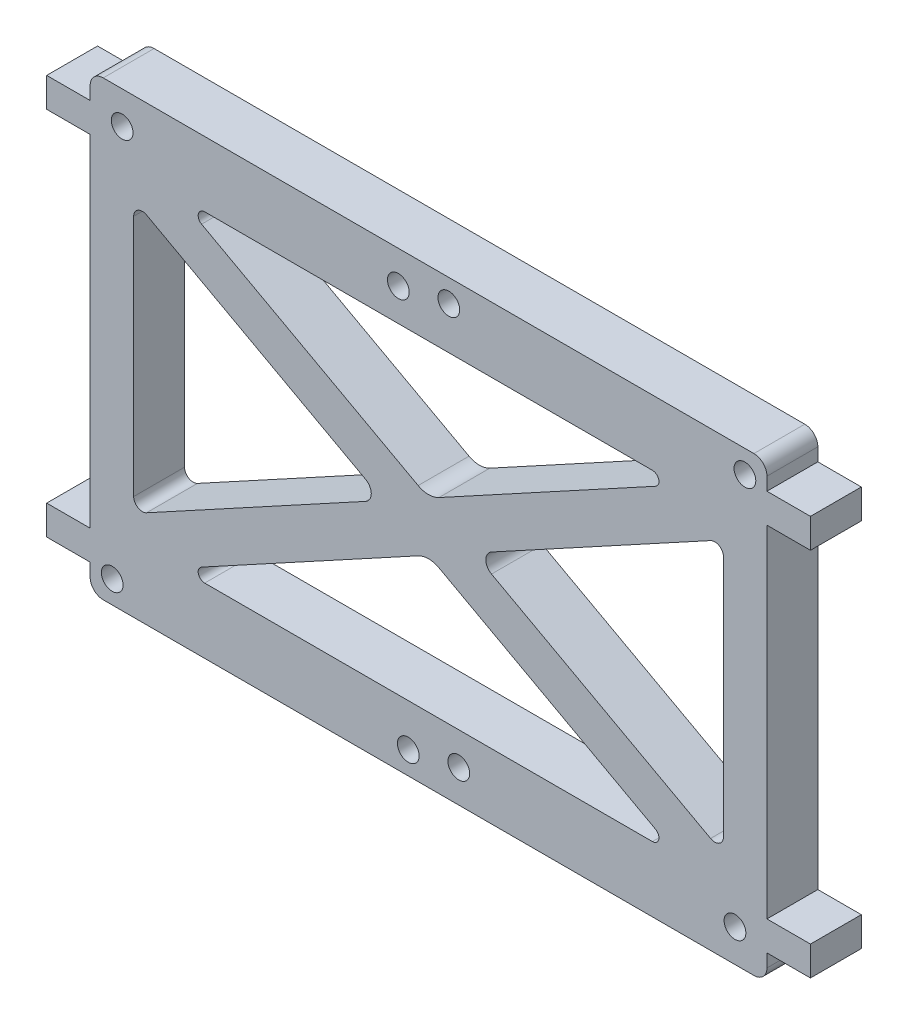
SolidWorks part; units mm, degrees
material "Acrylic (Medium-high impact)"
ref_plane "Front Plane" through (0, 0, 0) normal (0, 0, 1) x (1, 0, 0)
ref_plane "Top Plane" through (0, 0, 0) normal (0, 1, 0) x (1, 0, 0)
ref_plane "Right Plane" through (0, 0, 0) normal (1, 0, 0) x (0, 0, -1)
sketch "Sketch1" plane through (0, 0, 0) normal (0, 0, 1) x (1, 0, 0)
  line L0 (-1000, 0) -> (49000, 0) construction
  line L1 (-38.9, 22.98) -> (-38.9, 24.48)
  line L2 (-38.9, 19.6) -> (-38.9, -19.6)
  line L3 (-38.9, 19.6) -> (-43.9, 19.6)
  line L4 (-43.9, 19.6) -> (-43.9, 22.98)
  line L5 (-43.9, 22.98) -> (-38.9, 22.98)
  line L6 (-43.9, -22.98) -> (-38.9, -22.98)
  line L7 (-43.9, -19.6) -> (-43.9, -22.98)
  line L8 (-38.9, -19.6) -> (-43.9, -19.6)
  line L9 (-37.4, 25.98) -> (37.4, 25.98)
  line L10 (38.9, 24.48) -> (38.9, 22.98)
  line L11 (38.9, -24.48) -> (38.9, -22.98)
  line L12 (43.9, -22.98) -> (38.9, -22.98)
  line L13 (43.9, -19.6) -> (43.9, -22.98)
  line L14 (38.9, -19.6) -> (43.9, -19.6)
  line L15 (38.9, 19.6) -> (38.9, -19.6)
  line L16 (38.9, 19.6) -> (43.9, 19.6)
  line L17 (43.9, 19.6) -> (43.9, 22.98)
  line L18 (43.9, 22.98) -> (38.9, 22.98)
  line L19 (-38.9, -22.98) -> (-38.9, -24.48)
  line L20 (-37.4, -25.98) -> (37.4, -25.98)
  arc A0 (-38.9, -24.48) -> (-37.4, -25.98) centre (-37.4, -24.48) ccw
  arc A1 (37.4, -25.98) -> (38.9, -24.48) centre (37.4, -24.48) ccw
  arc A2 (38.9, 24.48) -> (37.4, 25.98) centre (37.4, 24.48) ccw
  arc A3 (-38.9, 24.48) -> (-37.4, 25.98) centre (-37.4, 24.48) cw
  point P4 (-38.9, 0)
  point P18 (-38.9, -25.98)
  point P21 (38.9, -25.98)
  point P24 (38.9, 25.98)
  point P27 (-38.9, 25.98)
  dimension "D5" = 1.5
  dimension "D1" = 3
  dimension "D2" = 39.2
  dimension "D3" = 3.38
  dimension "D4" = 5
extrude "Boss-Extrude1" add sketch "Sketch1" along normal blind 5.85
sketch "Sketch3" plane through (0, 0, 7.35) normal (0, 0, 1) x (1, 0, 0)
  line L0 (0, 25.98) -> (0, -25.98) construction
  line L1 (37.4, 25.98) -> (-37.4, 25.98) construction
  line L2 (-37.4, -25.98) -> (37.4, -25.98) construction
  circle A0 centre (-35.225, 22.225) radius 1.25
  circle A1 centre (-3.475, 22.225) radius 1.25
  circle A2 centre (-2.332, -23.368) radius 1.25
  circle A3 centre (-36.368, -23.368) radius 1.25
  circle A6 centre (2.332, 23.368) radius 1.25
  circle A7 centre (36.368, 23.368) radius 1.25
  circle A8 centre (35.225, -22.225) radius 1.25
  circle A9 centre (3.475, -22.225) radius 1.25
extrude "Cut-Extrude1" cut sketch "Sketch3" against normal through all
sketch "Sketch5" plane through (0, 0, 5.85) normal (0, 0, 1) x (1, 0, 0)
  line L0 (-38.9, 19.6) -> (-38.9, -19.6) construction
  line L1 (25.734, -18.48) -> (-25.734, -18.48)
  line L2 (33.9, -13.9486) -> (33.9, 13.9486)
  line L3 (25.734, 18.48) -> (-25.734, 18.48)
  line L4 (-33.9, -13.9486) -> (-33.9, 13.9486)
  line L5 (33.9, -18.48) -> (-33.9, 18.48) construction
  line L6 (33.9, 18.48) -> (-33.9, -18.48) construction
  line L7 (37.4, 25.98) -> (-37.4, 25.98) construction
  line L8 (-7.2365, -1.0975) -> (-32.4214, -14.8266)
  line L9 (-0.5983, 0) -> (-3.2099, 0) construction
  line L10 (-7.2365, 1.0975) -> (-32.4214, 14.8266)
  line L11 (0, -25.98) -> (0, 25.0508) construction
  line L12 (-1.1966, 3.4996) -> (-26.093, 17.0715)
  line L13 (1.1966, -3.4996) -> (26.093, -17.0715)
  line L14 (7.2365, -1.0975) -> (32.4214, -14.8266)
  line L15 (-1.1966, -3.4996) -> (-26.093, -17.0715)
  line L16 (7.2365, 1.0975) -> (32.4214, 14.8266)
  line L17 (1.1966, 3.4996) -> (26.093, 17.0715)
  arc A0 (7.2365, -1.0975) -> (7.2365, 1.0975) centre (7.8348, 0) cw
  arc A1 (-7.2365, -1.0975) -> (-7.2365, 1.0975) centre (-7.8348, 0) ccw
  arc A2 (1.1966, -3.4996) -> (-1.1966, -3.4996) centre (0, -5.6947) ccw
  arc A3 (1.1966, 3.4996) -> (-1.1966, 3.4996) centre (0, 5.6947) cw
  arc A4 (32.4214, -14.8266) -> (33.9, -13.9486) centre (32.9, -13.9486) ccw
  arc A5 (33.9, 13.9486) -> (32.4214, 14.8266) centre (32.9, 13.9486) ccw
  arc A6 (-33.9, 13.9486) -> (-32.4214, 14.8266) centre (-32.9, 13.9486) cw
  arc A7 (-32.4214, -14.8266) -> (-33.9, -13.9486) centre (-32.9, -13.9486) cw
  arc A8 (-25.734, 18.48) -> (-26.093, 17.0715) centre (-25.734, 17.73) ccw
  arc A9 (26.093, 17.0715) -> (25.734, 18.48) centre (25.734, 17.73) ccw
  arc A10 (25.734, -18.48) -> (26.093, -17.0715) centre (25.734, -17.73) ccw
  arc A11 (-25.734, -18.48) -> (-26.093, -17.0715) centre (-25.734, -17.73) cw
  point P0 (0, 0)
  point P28 (5.2232, 0)
  point P31 (-5.2232, 0)
  point P34 (0, -2.8473)
  point P37 (0, 2.8473)
  dimension "D6" = 1.25
  dimension "D7" = 2.5
  dimension "D8" = 1
  dimension "D9" = 0.75
  dimension "D1" = 5
  dimension "D2" = 7.5
  dimension "D3" = 2.5
  dimension "D4" = 2.5
  dimension "D5" = 2.5
extrude "Cut-Extrude2" cut sketch "Sketch5" against normal through all
